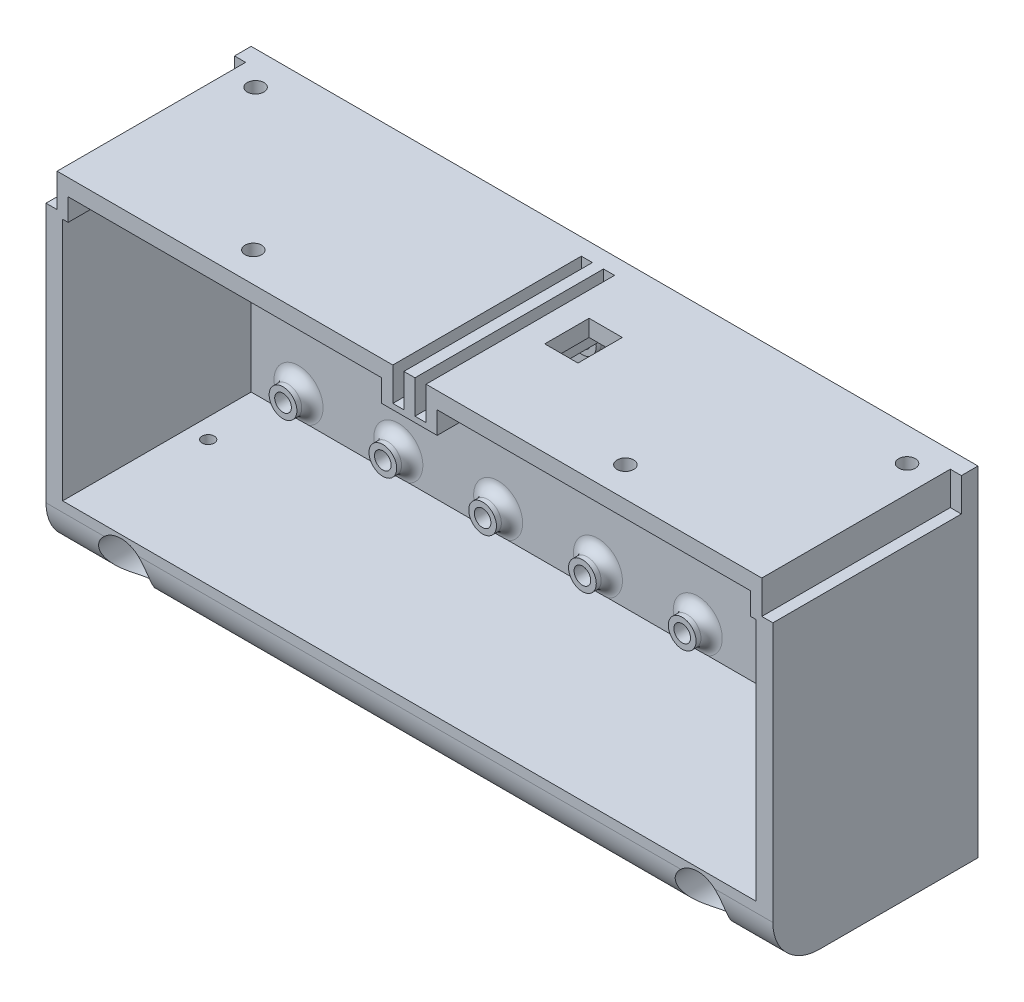
SolidWorks part; units mm, degrees
material "ABS"
ref_plane "Alzado" through (0, 0, 0) normal (0, 0, 1) x (1, 0, 0)
ref_plane "Planta" through (0, 0, 0) normal (0, 1, 0) x (1, 0, 0)
ref_plane "Vista lateral" through (0, 0, 0) normal (1, 0, 0) x (0, 0, -1)
sketch "Croquis2" plane through (0, 0, 0) normal (0, 0, 1) x (1, 0, 0)
  line L0 (0, 0) -> (131.1, 0)
  line L1 (131.1, 0) -> (131.1, -54)
  line L2 (131.1, -54) -> (0, -54)
  line L3 (0, -54) -> (0, 0)
  dimension "D1" = 131.1
  dimension "D2" = 54
extrude "Saliente-Extruir2" add sketch "Croquis2" along normal blind 3
sketch "Croquis3" plane through (0, 0, 3) normal (0, 0, 1) x (1, 0, 0)
  line L0 (0, -6) -> (2, -6)
  line L1 (0, 0) -> (0, -54) construction
  line L2 (2, -6) -> (2, 0)
  line L3 (131.1, 0) -> (0, 0) construction
  line L4 (2, 0) -> (129.1, 0)
  line L5 (129.1, 0) -> (129.1, -6)
  line L6 (129.1, -6) -> (131.1, -6)
  line L7 (131.1, -54) -> (131.1, 0) construction
  line L8 (131.1, -6) -> (131.1, -54)
  line L9 (131.1, -54) -> (0, -54)
  line L10 (0, -54) -> (0, -6)
  line L11 (65.55, 0) -> (66.55, 0)
  line L12 (65.55, 0) -> (64.55, 0)
  line L13 (64.55, 0) -> (64.55, -6)
  line L14 (66.55, 0) -> (66.55, -6)
  line L15 (64.55, -6) -> (62.55, -6)
  line L16 (62.55, -6) -> (62.55, 0)
  line L17 (66.55, -6) -> (68.55, -6)
  line L18 (68.55, -6) -> (68.55, 0)
  line L19 (3, -7) -> (128.1, -7)
  line L20 (128.1, -7) -> (128.1, -51)
  line L21 (128.1, -51) -> (3, -51)
  line L22 (3, -51) -> (3, -7)
  point P31 (130.1, -6)
  line M15 (0, 0) -> (0, -54)
  line M16 (0, -54) -> (131.1, -54)
  line M17 (131.1, -54) -> (131.1, 0)
  line M18 (131.1, 0) -> (0, 0)
  dimension "D1" = 2
  dimension "D2" = 2
  dimension "D3" = 6
  dimension "D4" = 2
  dimension "D5" = 2
  dimension "D6" = 1
  dimension "D7" = 1
  dimension "D8" = 3
  dimension "D9" = 3
  dimension "D10" = 3
  dimension "D11" = 1
extrude "Saliente-Extruir3" add sketch "Croquis3" along normal blind 34 contours L18 L17 L14 L4 L13 L15 L16 L2 L0 L6 L5 L21 L22 L19 L20 M18 M15 M16 M17 region at (1, -7.4179, 3)
sketch "Croquis4" plane through (0, -54, 0) normal (0, -1, 0) x (1, 0, 0)
  line L4 (0, 0) -> (131.1, 0)
  line L5 (131.1, 0) -> (131.1, 37)
  line L6 (131.1, 37) -> (0, 37)
  line L7 (0, 37) -> (0, 0)
  line L8 (0, 0) -> (131.1, 0)
  line L9 (131.1, 0) -> (131.1, 37)
  line L10 (131.1, 37) -> (0, 37)
  line L11 (0, 37) -> (0, 0)
  dimension "D1" = 0
extrude "Saliente-Extruir4" add sketch "Croquis4" along normal blind 7.2
sketch "Croquis5" plane through (0, 0, 37) normal (0, 0, 1) x (1, 0, 0)
  line L0 (3, -7) -> (128.1, -7) construction
  line L1 (4, -7) -> (60.55, -7)
  line L2 (4, -7) -> (4, -3)
  line L3 (4, -3) -> (60.55, -3)
  line L4 (60.55, -7) -> (60.55, -3)
  line L5 (62.55, 0) -> (2, 0) construction
  line L6 (65.55, -7) -> (65.55, 0) construction
  line L7 (66.55, 0) -> (64.55, 0) construction
  line L8 (127.1, -3) -> (70.55, -3)
  line L9 (70.55, -7) -> (70.55, -3)
  line L10 (127.1, -7) -> (70.55, -7)
  line L11 (127.1, -7) -> (127.1, -3)
  dimension "D1" = 1
  dimension "D2" = 2
  dimension "D3" = 3
extrude "Cortar-Extruir1" cut sketch "Croquis5" against normal up to vertex (34 mm away) up to point (3, -7, 3)
sketch "Croquis6" plane through (0, -3, 0) normal (0, -1, 0) x (1, 0, 0)
  line L0 (60.55, 37) -> (4, 37) construction
  line L1 (0, 37) -> (0, 3) construction
  line L2 (131.1, 37) -> (131.1, 3) construction
  line L3 (131.1, 0) -> (0, 0) construction
  line L4 (127.1, 3) -> (70.55, 3) construction
  line L5 (72.95, 20) -> (78.95, 20)
  line L6 (72.95, 20) -> (72.95, 12)
  line L7 (72.95, 12) -> (78.95, 12)
  line L8 (78.95, 20) -> (78.95, 12)
  circle A0 centre (32, 31.6) radius 1.5
  circle A1 centre (99.1, 31.6) radius 1.5
  circle A2 centre (6.8, 6) radius 1.5
  circle A3 centre (124.3, 6) radius 1.5
  point P16 (63.45, 31.6)
  dimension "D3" = 3
  dimension "D1" = 5.4
  dimension "D2" = 32
  dimension "D4" = 32
  dimension "D5" = 6.8
  dimension "D6" = 6
  dimension "D7" = 6.8
  dimension "D8" = 63.45
  dimension "D9" = 4.4
  dimension "D10" = 9
  dimension "D11" = 6
  dimension "D12" = 8
extrude "Cortar-Extruir2" cut sketch "Croquis6" against normal up to next
sketch "Croquis8" plane through (0, 0, 37) normal (0, 0, 1) x (1, 0, 0)
  line L0 (65.55, -61.2) -> (65.55, -51) construction
  line L1 (131.1, -61.2) -> (0, -61.2) construction
  line L2 (128.1, -51) -> (3, -51) construction
  circle A0 centre (13.55, -56.1) radius 4.5
  circle A1 centre (117.55, -56.1) radius 4.5
  point P8 (65.55, -56.1)
  dimension "D1" = 9
  dimension "D2" = 52
extrude "Cortar-Extruir3" cut sketch "Croquis8" against normal blind 33
sketch "Croquis9" plane through (0, 0, 37) normal (0, 0, 1) x (1, 0, 0)
  circle A0 centre (13.55, -56.1) radius 2.5
  circle A1 centre (117.55, -56.1) radius 2.5
  dimension "D1" = 5
extrude "Cortar-Extruir4" cut sketch "Croquis9" against normal through all
fillet "Redondeo1" radius 8.4 1 edges at (65.55, -61.2, 37)
sketch "Croquis10" plane through (0, 0, 3) normal (0, 0, 1) x (1, 0, 0)
  line L0 (60.55, -7) -> (70.55, -7) construction
  line L1 (60.55, -7) -> (70.55, -7) construction
  circle A0 centre (65.55, -10) radius 2.5
  circle A1 centre (65.55, -10) radius 1.5
  circle A2 centre (83.55, -10) radius 1.5
  circle A3 centre (83.55, -10) radius 2.5
  circle A4 centre (101.55, -10) radius 1.5
  circle A5 centre (101.55, -10) radius 2.5
  circle A6 centre (119.55, -10) radius 1.5
  circle A7 centre (119.55, -10) radius 2.5
  circle A8 centre (83.55, -47) radius 1.5
  circle A9 centre (83.55, -47) radius 2.5
  circle A10 centre (101.55, -47) radius 1.5
  circle A11 centre (101.55, -47) radius 2.5
  circle A12 centre (119.55, -47) radius 1.5
  circle A13 centre (119.55, -47) radius 2.5
  circle A16 centre (47.55, -10) radius 2.5
  circle A17 centre (47.55, -10) radius 1.5
  circle A18 centre (29.55, -10) radius 2.5
  circle A19 centre (29.55, -10) radius 1.5
  circle A20 centre (11.55, -10) radius 2.5
  circle A21 centre (11.55, -10) radius 1.5
  circle A22 centre (47.55, -47) radius 2.5
  circle A23 centre (47.55, -47) radius 1.5
  circle A24 centre (29.55, -47) radius 2.5
  circle A25 centre (29.55, -47) radius 1.5
  circle A26 centre (11.55, -47) radius 2.5
  circle A27 centre (11.55, -47) radius 1.5
  circle A28 centre (65.55, -47) radius 2.5
  circle A29 centre (65.55, -47) radius 1.5
  circle A30 centre (65.55, -47) radius 2.5 [skipped]
  circle A31 centre (65.55, -47) radius 1.5 [skipped]
  point P5 (65.55, -7)
  dimension "D1" = 5
  dimension "D3" = 3
  dimension "D2" = 3
  dimension "D4" = 4
  dimension "D5" = 2
  dimension "D6" = 4
  dimension "D7" = 2
extrude "Saliente-Extruir5" add sketch "Croquis10" along normal blind 2.8
fillet "Redondeo2" radius 1.92 14 edges at (9.05, -47, 3) (27.05, -47, 3) (45.05, -47, 3) (63.05, -47, 3) (81.05, -47, 3) (99.05, -47, 3) (117.05, -47, 3) (117.05, -10, 3) (99.05, -10, 3) (81.05, -10, 3) (63.05, -10, 3) (45.05, -10, 3) (27.05, -10, 3) (9.05, -10, 3)
sketch "Croquis11" plane through (0, -61.2, 0) normal (0, -1, 0) x (1, 0, 0)
  line L0 (0, 28.6) -> (0, 0) construction
  line L1 (0, 0) -> (131.1, 0) construction
  line L2 (65.55, 0) -> (65.55, 28.6) construction
  line L3 (131.1, 28.6) -> (0, 28.6) construction
  circle A0 centre (6.55, 14.3) radius 1.1
  circle A1 centre (124.55, 14.3) radius 1.1
  dimension "D3" = 2.2
  dimension "D1" = 6.55
  dimension "D2" = 14.3
extrude "Cortar-Extruir5" cut sketch "Croquis11" against normal up to next
